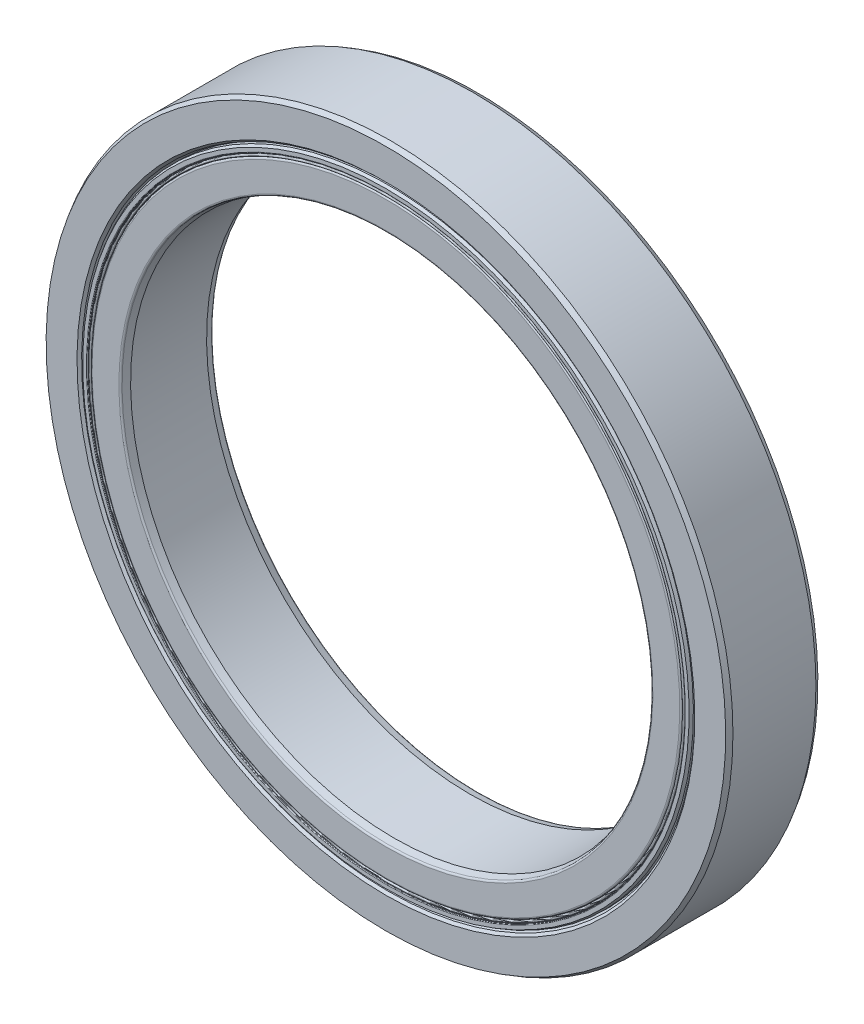
SolidWorks part; units mm, degrees
ref_plane "Front Plane" through (0, 0, 0) normal (0, 0, 1) x (1, 0, 0)
ref_plane "Top Plane" through (0, 0, 0) normal (0, 1, 0) x (1, 0, 0)
ref_plane "Right Plane" through (0, 0, 0) normal (1, 0, 0) x (0, 0, -1)
sketch "Sketch1" plane through (0, 0, 0) normal (0, 0, 1) x (1, 0, 0)
  line L0 (-26, 0) -> (26, 0) construction
  line L1 (-20, 0) -> (20, 0) construction
  circle A0 centre (0, 0) radius 20 construction
  circle A1 centre (0, 0) radius 26 construction
  point P3 (0, 0)
  point P6 (0, 0)
  point P7 (0, -20)
  point P11 (0, -26)
  point P12 (0, 20)
  point P13 (0, 26)
  dimension "OD" = 52
  dimension "ID" = 40
sketch "Sketch2" plane through (0, 0, 0) normal (1, 0, 0) x (0, 0, -1)
  line L0 (-3.5, 26) -> (3.5, 26) construction
  line L1 (0, 26) -> (0, -26) construction
  line L2 (3.15, 26) -> (-3.15, 26)
  line L3 (-3.15, 26) -> (-3.5, 25.7979)
  line L4 (-3.5, 25.7979) -> (-3.5, 23.4532)
  line L5 (-2.9452, 23.14) -> (-2.2237, 23.14)
  line L6 (2.9452, 23.14) -> (2.2237, 23.14)
  line L7 (3.5, 25.7979) -> (3.5, 23.4532)
  line L8 (3.15, 26) -> (3.5, 25.7979)
  line L9 (-2.2237, 23.14) -> (-2.2237, 24.0933) construction
  line L10 (-2.2237, 24.0933) -> (-2.2237, 25.0467) construction
  line L11 (0, 26) -> (0, -26) construction
  line L12 (-3.5, 0) -> (3.5, 0) construction
  line L13 (3.5, 20) -> (-3.5, 20) construction
  line L14 (-3.5, 20) -> (-3.5, -20) construction
  line L15 (-3.5, -20) -> (3.5, -20) construction
  line L16 (3.5, 26) -> (3.5, -26) construction
  line L17 (-2.2237, 25.0467) -> (-2.2237, 26) construction
  line L18 (-2.2237, 25.0467) -> (0, 25.0467) construction
  line L20 (-2.9452, 23.14) -> (-3.325, 23.2782)
  line L21 (-3.325, 23.2782) -> (-3.5, 23.4532)
  line L26 (3.325, 23.2782) -> (3.5, 23.4532)
  line L27 (2.9452, 23.14) -> (3.325, 23.2782)
  arc A0 (-2.2237, 23.14) -> (2.2237, 23.14) centre (0, 22.7967) cw
  circle A1 centre (0, 22.7967) radius 2.25 construction
  point P17 (0, 0)
  point P21 (0, 26)
  point P30 (0, -20)
  dimension "Approx. Ball Dia." = 4.5
  dimension "Width" = 7
  dimension "For Shaft Diameter" = 40
  dimension "For Housing ID" = 52
  dimension "D4" = 46.28
  dimension "D2" = 20
  dimension "D5" = 45
  dimension "D1" = 30
  dimension "D6" = 0.35
  dimension "D7" = 0.175
sketch "Sketch3" plane through (0, 0, 0) normal (1, 0, 0) x (0, 0, -1)
  line L14 (-2.9452, 23.14) -> (-3.325, 23.2782) construction
  line L15 (-3.325, 23.2782) -> (-3.5, 23.4532) construction
  line L16 (-3.5, 25.7979) -> (-3.5, 23.4532) construction
  line L17 (-3.15, 26) -> (-3.5, 25.7979) construction
  line L18 (3.15, 26) -> (-3.15, 26) construction
  line L19 (3.15, 26) -> (3.5, 25.7979) construction
  line L20 (3.5, 25.7979) -> (3.5, 23.4532) construction
  line L21 (3.325, 23.2782) -> (3.5, 23.4532) construction
  line L22 (2.9452, 23.14) -> (3.325, 23.2782) construction
  line L23 (2.9452, 23.14) -> (2.2237, 23.14) construction
  line L24 (-2.9452, 23.14) -> (-2.2237, 23.14) construction
  line L25 (-2.9452, 23.14) -> (-3.325, 23.2782)
  line L26 (-3.325, 23.2782) -> (-3.5, 23.4532)
  line L27 (-3.5, 25.7979) -> (-3.5, 23.4532)
  line L28 (-3.15, 26) -> (-3.5, 25.7979)
  line L29 (3.15, 26) -> (-3.15, 26)
  line L30 (3.15, 26) -> (3.5, 25.7979)
  line L31 (3.5, 25.7979) -> (3.5, 23.4532)
  line L32 (3.325, 23.2782) -> (3.5, 23.4532)
  line L33 (2.9452, 23.14) -> (3.325, 23.2782)
  line L34 (2.9452, 23.14) -> (2.2237, 23.14)
  line L35 (-2.9452, 23.14) -> (-2.2237, 23.14)
  arc A2 (2.2237, 23.14) -> (-2.2237, 23.14) centre (0, 22.7967) ccw construction
  arc A3 (2.2237, 23.14) -> (-2.2237, 23.14) centre (0, 22.7967) ccw
revolve "Revolve1" add sketch "Sketch3" angle 360 about L12
sketch "Sketch4" plane through (0, 0, 0) normal (1, 0, 0) x (0, 0, -1)
  line L0 (0, 26) -> (0, -26) construction
  line L1 (0, 26) -> (0, -26) construction
  line L2 (-2.8851, 20) -> (-3.3951, 20.1367)
  line L3 (-3.5, 20.2733) -> (-3.5, 22.3118)
  line L4 (3.5, -25.7979) -> (3.5, 25.7979) construction
  line L5 (-3.3585, 22.4533) -> (-2.2237, 22.4533)
  line L6 (-2.8851, 20) -> (2.8851, 20)
  line L7 (3.5, 25.7979) -> (3.5, 23.4532) construction
  line L8 (2.8851, 20) -> (3.3951, 20.1367)
  line L9 (0, 25.0467) -> (0, 20) construction
  line L10 (3.5, 20.2733) -> (3.5, 22.3118)
  line L11 (3.3585, 22.4533) -> (2.2237, 22.4533)
  line L12 (2.8851, 20) -> (2.8851, 20.1367) construction
  line L13 (2.8851, 20.1367) -> (2.8851, 20.2733) construction
  line L14 (2.8851, 20.2733) -> (2.8851, 20.41) construction
  line L15 (2.8851, 20.41) -> (2.8851, 20.5467) construction
  circle A0 centre (0, 22.7967) radius 2.25 construction
  arc A1 (2.2237, 22.4533) -> (-2.2237, 22.4533) centre (0, 22.7967) cw
  arc A2 (3.5, 22.3118) -> (3.3585, 22.4533) centre (3.3585, 22.3118) ccw
  arc A3 (-3.5, 22.3118) -> (-3.3585, 22.4533) centre (-3.3585, 22.3118) cw
  arc A4 (3.3951, 20.1367) -> (3.5, 20.2733) centre (3.3585, 20.2733) ccw
  arc A5 (-3.3951, 20.1367) -> (-3.5, 20.2733) centre (-3.3585, 20.2733) cw
  point P14 (3.5, 20.1648)
  point P36 (0, 20.5467)
  dimension "D1" = 15
revolve "Revolve2" add sketch "Sketch4" angle 360 about L12
sketch "Sketch5" plane through (0, 0, 0) normal (1, 0, 0) x (0, 0, -1)
  line L0 (-2.25, 22.7967) -> (2.25, 22.7967)
  arc A2 (-2.25, 22.7967) -> (2.25, 22.7967) centre (0, 22.7967) cw
  arc A3 (2.2237, 23.14) -> (-2.2237, 23.14) centre (0, 22.7967) ccw construction
revolve "Revolve3" add sketch "Sketch5" angle 360 about L0
pattern_circular "CirPattern1" count 20 over 360 about axis through (0, 0, 3.5) along (0, 0, -1) of bodies 104
sketch "Sketch6" plane through (0, 0, 0) normal (1, 0, 0) x (0, 0, -1)
  line L1 (-3.2922, 23.14) -> (-2.25, 23.14)
  line L2 (-3.5, 23.02) -> (-3.5, 22.7413)
  line L3 (-3.452, 22.6933) -> (-2.25, 22.6933)
  line L4 (-2.25, 23.14) -> (-2.25, 22.6933)
  line L5 (-3.5, 20.2733) -> (-3.5, 22.3118) construction
  line L6 (-3.15, 26) -> (-3.5, 25.7979) construction
  line L7 (0, 26) -> (0, 20) construction
  line L8 (3.452, 22.6933) -> (2.25, 22.6933)
  line L9 (2.25, 23.14) -> (2.25, 22.6933)
  line L10 (3.2922, 23.14) -> (2.25, 23.14)
  line L11 (3.5, 23.02) -> (3.5, 22.7413)
  line L13 (-3.3585, 22.4533) -> (-2.2237, 22.4533) construction
  line L14 (-3.5, 23.02) -> (-3.2922, 23.14)
  line L15 (-2.9452, 23.14) -> (-2.2237, 23.14) construction
  line L16 (3.5, 23.02) -> (3.2922, 23.14)
  arc A0 (-3.5, 22.7413) -> (-3.452, 22.6933) centre (-3.452, 22.7413) ccw
  circle A1 centre (0, 22.7967) radius 2.25 construction
  arc A2 (3.5, 22.7413) -> (3.452, 22.6933) centre (3.452, 22.7413) cw
  point P26 (-3.5, 22.6933)
  dimension "D3" = 0.048
  dimension "D1" = 0.24
  dimension "D2" = 0.12
revolve "Revolve4" add sketch "Sketch6" angle 360 about L12
sketch "Sketch7" plane through (0, 0, 0) normal (1, 0, 0) x (0, 0, -1)
  line L3 (-2.25, 22.6933) -> (-3.3302, 22.6933)
  line L4 (-3.452, 22.6933) -> (-2.25, 22.6933) construction
  line L7 (0, 20.5467) -> (0, 20) construction
  line L8 (0, 26) -> (0, -26) construction
  line L21 (-3.3302, 22.6933) -> (-3.3893, 22.6829)
  line L22 (-3.385, 22.6333) -> (-3.41, 22.6333)
  line L23 (-3.41, 22.4533) -> (-2.25, 22.4533)
  line L24 (-2.25, 22.4533) -> (-2.25, 22.6933)
  line L25 (-3.3585, 22.4533) -> (-2.2237, 22.4533) construction
  line L26 (-3.5, 22.7413) -> (-3.5, 22.4533) construction
  line L27 (-3.5, 22.4533) -> (-3.41, 22.4533) construction
  line L28 (-3.3302, 22.6933) -> (-3.3302, 22.6333) construction
  line L29 (-3.3302, 22.6333) -> (-3.3302, 22.5733) construction
  line L30 (-3.3302, 22.5733) -> (-3.3302, 22.5133) construction
  line L31 (-3.3302, 22.5133) -> (-3.3302, 22.4533) construction
  circle A2 centre (0, 22.7967) radius 2.25 construction
  arc A9 (-3.3893, 22.6829) -> (-3.385, 22.6333) centre (-3.385, 22.6583) ccw
  arc A10 (-3.41, 22.6333) -> (-3.41, 22.4533) centre (-3.41, 22.5433) ccw
  dimension "D1" = 0.025
  dimension "D2" = 10
revolve "Revolve5" add sketch "Sketch7" angle 360 about L12
ref_axis "Axis1" through (0, 0, -2.8851) along (0, 0, 1)
equation "\"D4@Sketch2\"=\"OD@Sketch1\"*.89"
equation "\"D1@Sketch6\"=(\"OD@Sketch1\"-\"ID@Sketch1\")*.02"
equation "\"D2@Sketch6\"=\"D1@Sketch6\"*.5"
equation "\"D3@Sketch6\"=\"D1@Sketch6\"*.2"
equation "\"D6@Sketch2\"=\"Width@Sketch2\"*.05"
equation "\"D7@Sketch2\"=\"D6@Sketch2\"*.5"
equation "\"D1@CirPattern1\" =  ( pi * \"OD@Sketch1\" )  * .5625 / \"Approx. Ball Dia.@Sketch2\""
equation "\"Approx. Ball Dia.@Sketch2\"=(\"OD@Sketch1\"-\"ID@Sketch1\")*.5*.75"
